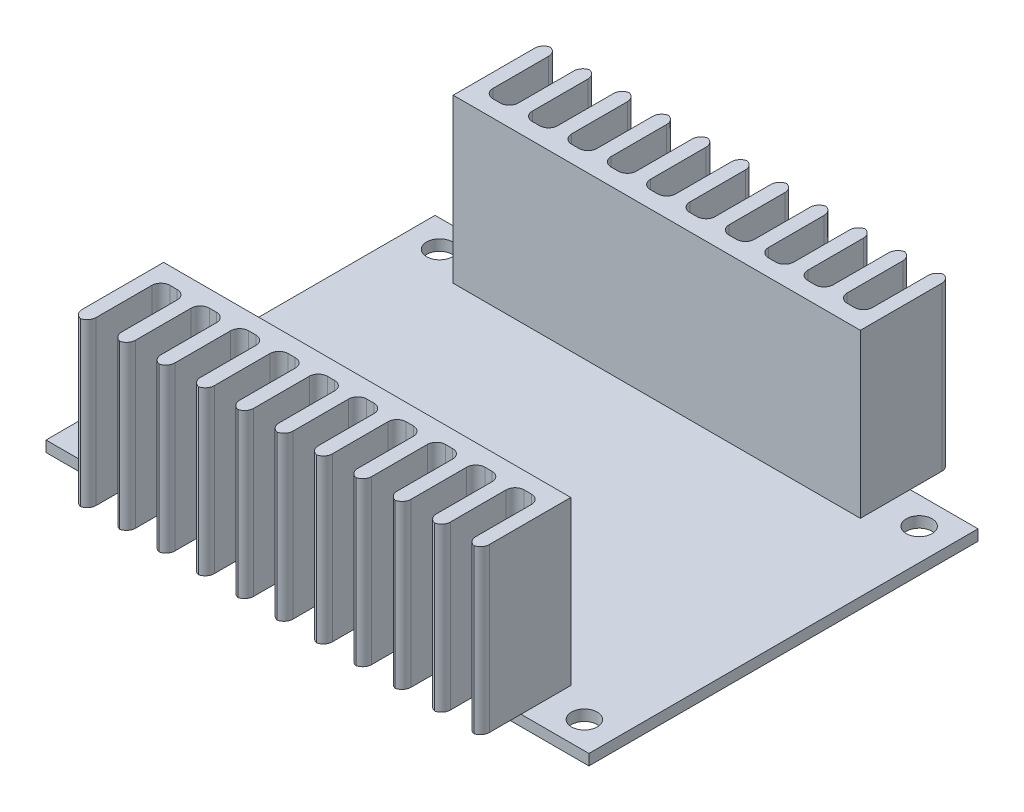
SolidWorks part; units mm, degrees
ref_plane "Plan de face" through (0, 0, 0) normal (0, 0, 1) x (1, 0, 0)
ref_plane "Plan de dessus" through (0, 0, 0) normal (0, 1, 0) x (1, 0, 0)
ref_plane "Plan de droite" through (0, 0, 0) normal (1, 0, 0) x (0, 0, -1)
sketch "Esquisse1" plane through (0, 0, 0) normal (0, 1, 0) x (1, 0, 0)
  line L0 (-30, 0) -> (30, 0) construction
  line L1 (-30, 21.5) -> (30, 21.5)
  line L2 (-30, 21.5) -> (-30, -21.5)
  line L3 (-30, -21.5) -> (30, -21.5)
  line L4 (30, 21.5) -> (30, -21.5)
  line L5 (0, 21.5) -> (0, -21.5) construction
  dimension "D1" = 60
  dimension "D2" = 43
extrude "Boss.-Extru.1" add sketch "Esquisse1" along normal blind 1.2
sketch "Esquisse2" plane through (0, 1.2, 0) normal (0, 1, 0) x (1, 0, 0)
  line L0 (0, 0) -> (0, -16) construction
  line L1 (-22.5, -16) -> (22.5, -16)
  line L2 (-22.5, -16) -> (-22.5, -26)
  line L3 (-22.5, -26) -> (22.5, -26)
  line L4 (22.5, -16) -> (22.5, -26)
  line L5 (-30, -21.5) -> (30, -21.5) construction
  dimension "D1" = 45
  dimension "D2" = 10
  dimension "D3" = 4.5
extrude "Boss.-Extru.2" add sketch "Esquisse2" along normal blind 18
sketch "Esquisse3" plane through (0, 19.2, 0) normal (0, 1, 0) x (1, 0, 0)
  line L0 (-22.5, -26) -> (22.5, -26) construction
  line L1 (-20.9545, -26) -> (-18.1545, -26)
  line L2 (-20.9545, -26) -> (-20.9545, -17.85)
  line L3 (-20.9545, -17.85) -> (-18.1545, -17.85)
  line L4 (-18.1545, -26) -> (-18.1545, -17.85)
  line L5 (-22.5, -16) -> (-22.5, -26) construction
  line L6 (-16.6045, -26) -> (-13.8045, -26)
  line L7 (-16.6045, -26) -> (-16.6045, -17.85)
  line L8 (-16.6045, -17.85) -> (-13.8045, -17.85)
  line L9 (-13.8045, -26) -> (-13.8045, -17.85)
  line L10 (-12.2545, -26) -> (-9.4545, -26)
  line L11 (-12.2545, -26) -> (-12.2545, -17.85)
  line L12 (-12.2545, -17.85) -> (-9.4545, -17.85)
  line L13 (-9.4545, -26) -> (-9.4545, -17.85)
  line L14 (-7.9045, -26) -> (-5.1045, -26)
  line L15 (-7.9045, -26) -> (-7.9045, -17.85)
  line L16 (-7.9045, -17.85) -> (-5.1045, -17.85)
  line L17 (-5.1045, -26) -> (-5.1045, -17.85)
  line L18 (-3.5545, -26) -> (-0.7545, -26)
  line L19 (-3.5545, -26) -> (-3.5545, -17.85)
  line L20 (-3.5545, -17.85) -> (-0.7545, -17.85)
  line L21 (-0.7545, -26) -> (-0.7545, -17.85)
  line L22 (0.7955, -26) -> (3.5955, -26)
  line L23 (0.7955, -26) -> (0.7955, -17.85)
  line L24 (0.7955, -17.85) -> (3.5955, -17.85)
  line L25 (3.5955, -26) -> (3.5955, -17.85)
  line L26 (5.1455, -26) -> (7.9455, -26)
  line L27 (5.1455, -26) -> (5.1455, -17.85)
  line L28 (5.1455, -17.85) -> (7.9455, -17.85)
  line L29 (7.9455, -26) -> (7.9455, -17.85)
  line L30 (9.4955, -26) -> (12.2955, -26)
  line L31 (9.4955, -26) -> (9.4955, -17.85)
  line L32 (9.4955, -17.85) -> (12.2955, -17.85)
  line L33 (12.2955, -26) -> (12.2955, -17.85)
  line L34 (13.8455, -26) -> (16.6455, -26)
  line L35 (13.8455, -26) -> (13.8455, -17.85)
  line L36 (13.8455, -17.85) -> (16.6455, -17.85)
  line L37 (16.6455, -26) -> (16.6455, -17.85)
  line L38 (18.1955, -26) -> (20.9955, -26)
  line L39 (18.1955, -26) -> (18.1955, -17.85)
  line L40 (18.1955, -17.85) -> (20.9955, -17.85)
  line L41 (20.9955, -26) -> (20.9955, -17.85)
  dimension "D1" = 2.8
  dimension "D2" = 1.5455
  dimension "D3" = 8.15
  dimension "D4" = 10
extrude "Enlèv. mat.-Extru.1" cut sketch "Esquisse3" against normal blind 18
fillet "Congé2" radius 1 42 edges at (18.1955, 10.2, 17.85) (13.8455, 10.2, 17.85) (9.4955, 10.2, 17.85) (5.1455, 10.2, 17.85) (0.7955, 10.2, 17.85) (-3.5545, 10.2, 17.85) (-7.9045, 10.2, 17.85) (-5.1045, 10.2, 17.85) (-0.7545, 10.2, 17.85) (3.5955, 10.2, 17.85) (7.9455, 10.2, 17.85) (12.2955, 10.2, 17.85) (16.6455, 10.2, 17.85) (20.9955, 10.2, 17.85) (22.5, 10.2, 26) (20.9955, 10.2, 26) (18.1955, 10.2, 26) (16.6455, 10.2, 26) (13.8455, 10.2, 26) (12.2955, 10.2, 26) (9.4955, 10.2, 26) (7.9455, 10.2, 26) (5.1455, 10.2, 26) (3.5955, 10.2, 26) (0.7955, 10.2, 26) (-0.7545, 10.2, 26) (-3.5545, 10.2, 26) (-5.1045, 10.2, 26) (-7.9045, 10.2, 26) (-9.4545, 10.2, 26) (-9.4545, 10.2, 17.85) (-12.2545, 10.2, 17.85) (-12.2545, 10.2, 26) (-13.8045, 10.2, 26) (-13.8045, 10.2, 17.85) (-16.6045, 10.2, 17.85) (-16.6045, 10.2, 26) (-18.1545, 10.2, 26) (-18.1545, 10.2, 17.85) (-20.9545, 10.2, 17.85) (-20.9545, 10.2, 26) (-22.5, 10.2, 26)
mirror "Symétrie1" about plane through (0, 0, 0) normal (0, 0, 1) of "Boss.-Extru.2", "Enlèv. mat.-Extru.1", "Congé2"
sketch "Esquisse4" plane through (0, 1.2, 0) normal (0, 1, 0) x (1, 0, 0)
  line L0 (26.5, -18.5) -> (26.5, 18.5) construction
  line L1 (-26.5, 18.5) -> (-26.5, -18.5) construction
  line L2 (-26.5, 0) -> (26.5, 0) construction
  circle A0 centre (-26.5, -18.5) radius 1.425
  circle A1 centre (-26.5, 18.5) radius 1.425
  circle A2 centre (26.5, 18.5) radius 1.425
  circle A3 centre (26.5, -18.5) radius 1.425
  dimension "D4" = 2.85
  dimension "D1" = 37
  dimension "D2" = 37
  dimension "D3" = 53
extrude "Enlèv. mat.-Extru.2" cut sketch "Esquisse4" against normal through all
